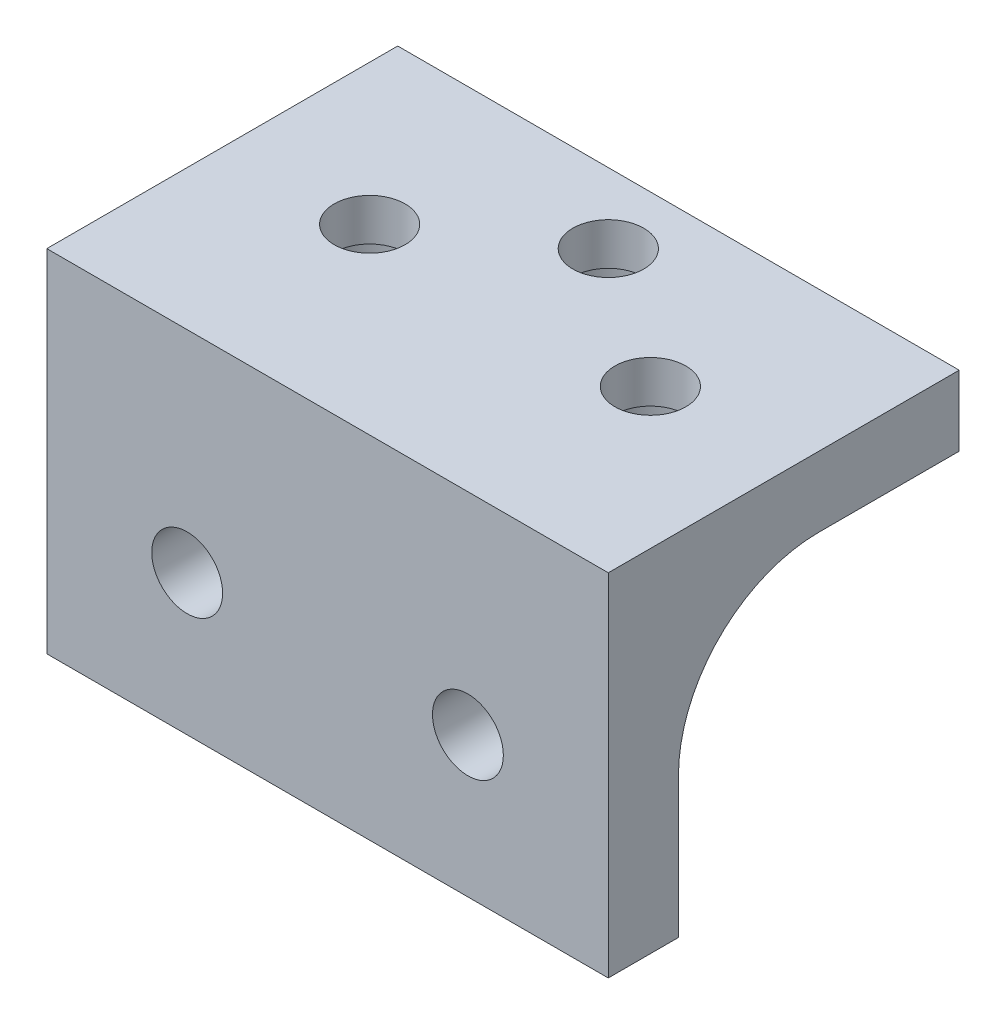
SolidWorks part; units mm, degrees
ref_plane "Alzado" through (0, 0, 0) normal (0, 0, 1) x (1, 0, 0)
ref_plane "Planta" through (0, 0, 0) normal (0, 1, 0) x (1, 0, 0)
ref_plane "Vista lateral" through (0, 0, 0) normal (1, 0, 0) x (0, 0, -1)
sketch "Croquis1" plane through (0, 0, 0) normal (0, 0, 1) x (1, 0, 0)
  line L0 (20, 20) -> (20, 0) construction
  line L1 (0, 0) -> (40, 0)
  line L2 (0, 0) -> (0, 25)
  line L3 (0, 25) -> (40, 25)
  line L4 (40, 0) -> (40, 25)
  line L5 (0, 25) -> (40, 25)
  line L6 (0, 25) -> (0, 20)
  line L7 (0, 20) -> (40, 20)
  line L8 (40, 25) -> (40, 20)
  line L9 (10, 10) -> (30, 10) construction
  circle A0 centre (10, 10) radius 2.525
  circle A1 centre (30, 10) radius 2.525
  point P11 (20, 10)
  point P14 (17.6412, 10)
  point P15 (15.4555, 10)
  point P17 (20, 10)
  dimension "D4" = 10
  dimension "D5" = 5.05
  dimension "D1" = 25
  dimension "D2" = 40
  dimension "D3" = 5
extrude "Saliente-Extruir1" add sketch "Croquis1" along normal blind 5 contours L7 L2 L1 L4 A1 A0 | L2 L7 L4 L3 region at (20, 10, 0) region at (20, 22.5, 0)
extrude "Saliente-Extruir2" add sketch "Croquis1<3>" against normal blind 20 contours L2 L7 L4 L3 region at (20, 22.5, 0)
sketch "Croquis1<3>" plane through (0, 0, 0) normal (0, 0, 1) x (1, 0, 0) same geometry as "Croquis1"
sketch "Croquis2" plane through (0, 20, 0) normal (0, -1, 0) x (1, 0, 0)
  line L0 (10, -8) -> (30, -8) construction
  line L1 (0, -20) -> (40, -20) construction
  line L2 (0, -20) -> (40, -20) construction
  line L4 (0, 0) -> (40, 0) construction
  circle A0 centre (10, -8) radius 2.525
  circle A1 centre (30, -8) radius 2.525
  circle A2 centre (20, -15) radius 2.525
  point P6 (0, 0)
  point P8 (20, -20)
  point P9 (20, -8)
  dimension "D1" = 5.05
  dimension "D3" = 10
  dimension "D2" = 8
  dimension "D4" = 7
extrude "Cortar-Extruir1" cut sketch "Croquis2" against normal through all
sketch "Croquis4" plane through (0, 20, 0) normal (0, -1, 0) x (1, 0, 0)
  circle A5 centre (10, -8) radius 4.025
  circle A6 centre (10, -8) radius 4.025
  circle A8 centre (20, -15) radius 4.025
  circle A9 centre (20, -15) radius 4.025
  circle A11 centre (30, -8) radius 4.025
  circle A12 centre (30, -8) radius 4.025
  dimension "D1" = 1.5
  dimension "D2" = 1.5
  dimension "D3" = 1.5
extrude "Cortar-Extruir2" cut sketch "Croquis4" against normal blind 2
fillet "Redondeo1" radius 10 1 edges at (20, 20, 0)
